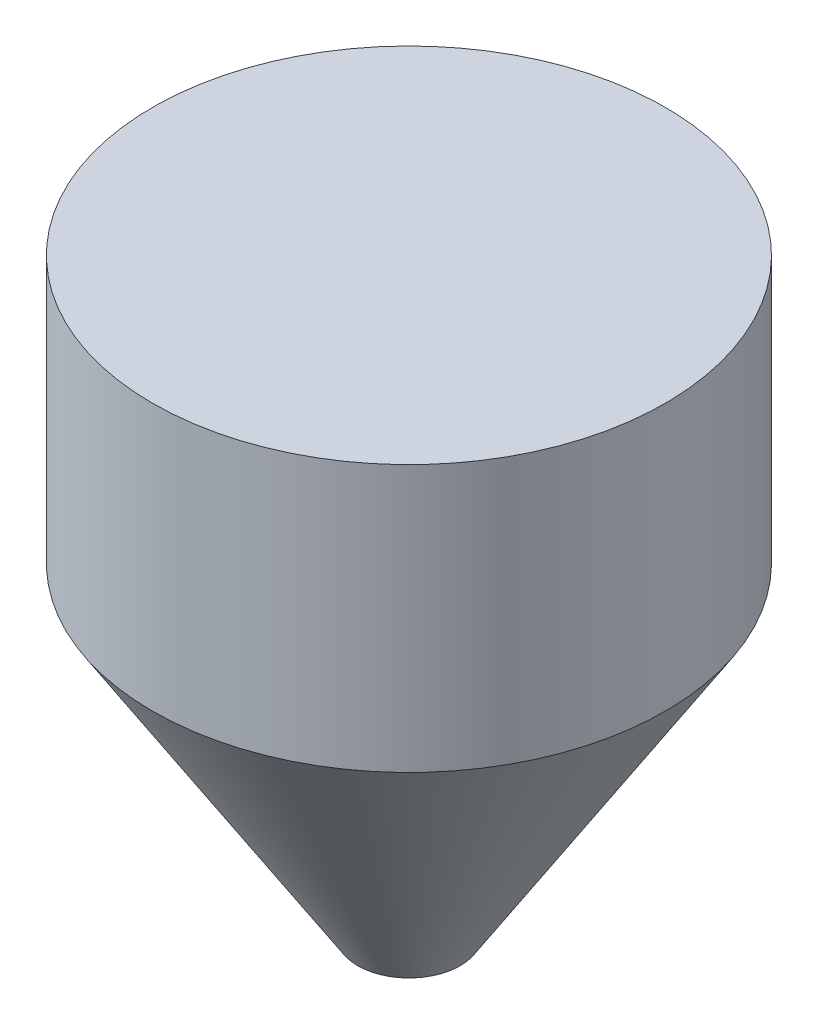
SolidWorks part; units mm, degrees
ref_plane "Alzado" through (0, 0, 0) normal (0, 0, 1) x (1, 0, 0)
ref_plane "Planta" through (0, 0, 0) normal (0, 1, 0) x (1, 0, 0)
ref_plane "Vista lateral" through (0, 0, 0) normal (1, 0, 0) x (0, 0, -1)
sketch "Croquis1" plane through (0, 0, 0) normal (0, 1, 0) x (1, 0, 0)
  circle A0 centre (0, 0) radius 100
  dimension "D1" = 200
ref_plane "Plano1" through (0, -230, 0) normal (0, 1, 0) x (1, 0, 0)
extrude "Saliente-Extruir1" add sketch "Croquis1" against normal blind 104 contours A0
sketch "Croquis2" plane through (0, -104, 0) normal (0, -1, 0) x (1, 0, 0)
  circle A2 centre (0, 0) radius 100
sketch "Croquis3" plane through (0, -230, 0) normal (0, 1, 0) x (1, 0, 0)
  circle A0 centre (0, 0) radius 20
  dimension "D1" = 40
loft "Recubrir1" add profiles "Croquis3", "Croquis2" connector at (-19.9701, -230, 1.0927) connector at (-99.8027, -104, 6.2791)
